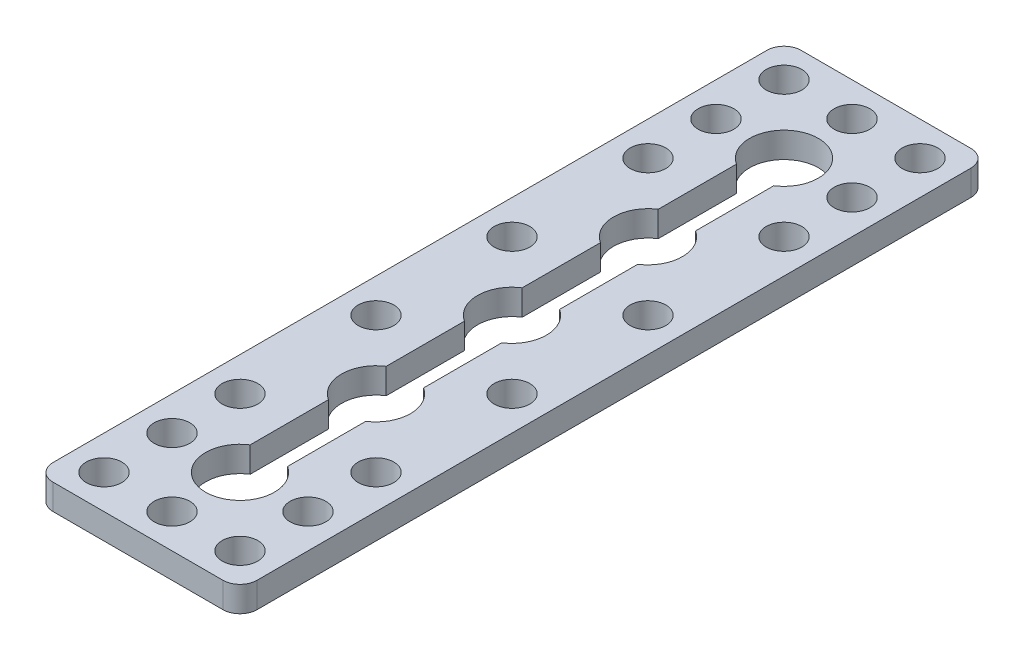
SolidWorks part; units mm, degrees
ref_plane "Front Plane" through (0, 0, 0) normal (0, 0, 1) x (1, 0, 0)
ref_plane "Top Plane" through (0, 0, 0) normal (0, 1, 0) x (1, 0, 0)
ref_plane "Right Plane" through (0, 0, 0) normal (1, 0, 0) x (0, 0, -1)
sketch "Sketch1" plane through (0, 0, 0) normal (0, 1, 0) x (1, 0, 0)
  line L1 (0, 0) -> (24, 0)
  line L2 (0, 0) -> (0, 88)
  line L3 (0, 88) -> (24, 88)
  line L4 (24, 0) -> (24, 88)
  dimension "D1" = 24
  dimension "D2" = 88
extrude "Boss-Extrude1" add sketch "Sketch1" along normal blind 3
sketch "Sketch2" plane through (0, 3, 0) normal (0, 1, 0) x (1, 0, 0)
  line L0 (12, 0) -> (12, 88) construction
  line L1 (0, 0) -> (24, 0) construction
  line L2 (24, 88) -> (0, 88) construction
  line L3 (0, 44) -> (24, 44) construction
  line L4 (0, 88) -> (0, 0) construction
  line L5 (24, 0) -> (24, 88) construction
  line L6 (4, 88) -> (4, 44) construction
  line L7 (4, 84) -> (12, 84) construction
  line L8 (4, 76) -> (12, 76) construction
  line L9 (4, 12) -> (12, 12) construction
  line L10 (4, 4) -> (12, 4) construction
  circle A0 centre (12, 84) radius 2.1
  circle A1 centre (4, 84) radius 2.1
  circle A2 centre (4, 76) radius 2.1
  circle A3 centre (4, 68) radius 2.1
  circle A4 centre (4, 52) radius 2.1
  circle A6 centre (20, 52) radius 2.1
  circle A7 centre (20, 68) radius 2.1
  circle A8 centre (20, 76) radius 2.1
  circle A9 centre (20, 84) radius 2.1
  circle A10 centre (20, 4) radius 2.1
  circle A11 centre (20, 12) radius 2.1
  circle A12 centre (20, 20) radius 2.1
  circle A13 centre (20, 36) radius 2.1
  circle A14 centre (4, 36) radius 2.1
  circle A15 centre (4, 20) radius 2.1
  circle A16 centre (4, 12) radius 2.1
  circle A17 centre (4, 4) radius 2.1
  circle A18 centre (12, 4) radius 2.1
  dimension "D1" = 4.2
  dimension "D2" = 16
  dimension "D3" = 16
  dimension "D4" = 8
  dimension "D5" = 16
  dimension "D6" = 16
extrude "Cut-Extrude1" cut sketch "Sketch2" against normal through all
sketch "Sketch3" plane through (0, 3, 0) normal (0, 1, 0) x (1, 0, 0)
  circle A0 centre (12, 76) radius 4.05
  dimension "D1" = 8.1
extrude "Cut-Extrude2" cut sketch "Sketch3" against normal through all
pattern_linear "LPattern1" count 5 spacing 16 along (0, 0, 1) of "Cut-Extrude2"
sketch "Sketch4" plane through (0, 3, 0) normal (0, 1, 0) x (1, 0, 0)
  line L1 (9.8, 76) -> (14.2, 76)
  line L2 (9.8, 76) -> (9.8, 12)
  line L3 (9.8, 12) -> (14.2, 12)
  line L4 (14.2, 76) -> (14.2, 12)
  point P4 (12, 76)
  point P6 (12, 12)
  dimension "D1" = 4.4
extrude "Cut-Extrude3" cut sketch "Sketch4" against normal through all
fillet "Fillet1" radius 2 4 edges at (24, 1.5, -88) (0, 1.5, -88) (0, 1.5, 0) (24, 1.5, 0)
equation "\"width\"= 24"
equation "\"thk\"= 3"
equation "\"holesize\"= 4.2"
equation "\"holedistance\"= ( 20 + 12 ) / 2"
equation "\"threaded_hole\"= 3.9"
equation "\"fillet_radius\"= 2"
equation "\"D1@Sketch1\"=\"width\""
equation "\"D1@Boss-Extrude1\"=\"thk\""
equation "\"D1@Sketch2\"=\"holesize\""
equation "\"D2@Sketch2\"=\"holedistance\""
equation "\"D3@Sketch2\"=\"holedistance\""
equation "\"D4@Sketch2\"=\"holedistance\"/2"
equation "\"D5@Sketch2\"=\"holedistance\""
equation "\"D6@Sketch2\"=\"holedistance\""
equation "\"D1@Fillet1\"=\"fillet_radius\""
